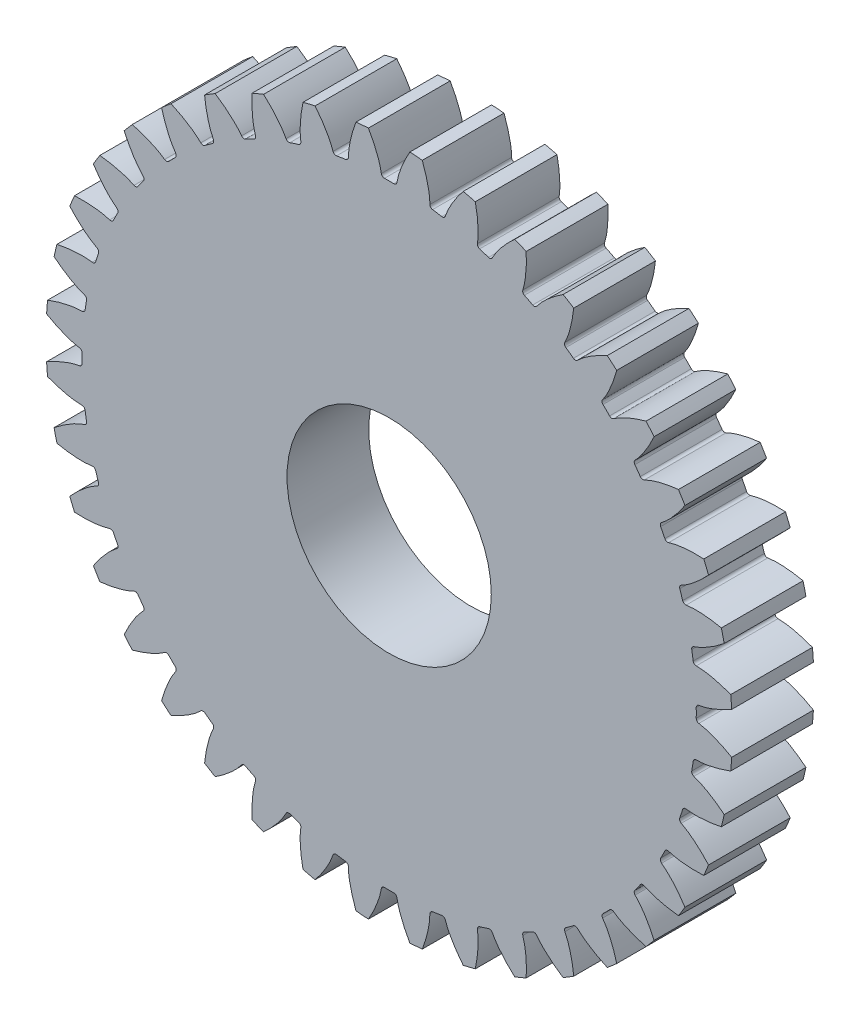
SolidWorks part; units mm, degrees
ref_plane "前视基准面" through (0, 0, 0) normal (0, 0, 1) x (1, 0, 0)
ref_plane "上视基准面" through (0, 0, 0) normal (0, 1, 0) x (1, 0, 0)
ref_plane "右视基准面" through (0, 0, 0) normal (1, 0, 0) x (0, 0, -1)
other "Configuration Table"
sketch "circles" plane through (0, 0, 0) normal (0, 0, 1) x (1, 0, 0)
  circle A0 centre (0, 0) radius 42
  circle A1 centre (0, 0) radius 37.5
  circle A2 centre (0, 0) radius 37.5877
  circle A3 centre (0, 0) radius 40
  dimension "D1" = 80
  dimension "D2" = 75.1754
  dimension "D3" = 75
  dimension "D4" = 84
extrude "Gear_extrude" add sketch "circles" along normal blind 10 contours A0
sketch "Involute" plane through (0, 0, 10) normal (0, 0, 1) x (1, 0, 0)
  spline S0 degree 4 poles (37.5765, -0.9158) (37.645, -0.9197) (37.8365, -0.9378) (38.1956, -0.9998) (38.7736, -1.1397) (39.4958, -1.3743) (40.4079, -1.7407) (41.4503, -2.2517) (42.5565, -2.8942) (44.0013, -3.8723) (45.3632, -4.9668) (46.643, -6.1553) (48.0474, -7.6399) (49.3628, -9.2047) (50.7742, -11.1387) (52.2189, -13.4708) (53.5152, -15.946) (54.6413, -18.5029) (55.482, -20.7981) (56.1023, -22.7989) (56.5537, -24.4844) (56.8762, -25.8433) (57.2316, -27.5509) (57.5244, -29.2733) (57.7561, -31.0004) (57.9277, -32.7411) (58.03, -34.1262) (58.0885, -35.3596) (58.118, -36.3844) (58.1271, -37.2927) (58.1284, -37.9211) (58.117, -38.7156) (58.1053, -39.2113) (58.0822, -39.9153) (58.058, -40.4457) (58.0262, -41.0523) (57.9901, -41.6142) (57.9477, -42.2028) (57.9003, -42.7733) (57.8604, -43.2108) (57.8321, -43.4973) (57.8175, -43.6418) knots 0 0 0 0 0 0.005377 0.015084 0.028532 0.04661 0.064855 0.092111 0.119476 0.146842 0.201575 0.228941 0.256307 0.307035 0.361767 0.4165 0.471232 0.525964 0.580697 0.608063 0.635429 0.662795 0.690161 0.744894 0.77226 0.799626 0.826992 0.854358 0.868042 0.881725 0.895408 0.909091 0.920455 0.931818 0.943182 0.954545 0.965909 0.977273 0.988636 1 1 1 1 1 construction
  spline S2 degree 4 poles (37.5765, 0.9158) (37.645, 0.9197) (37.8365, 0.9378) (38.1956, 0.9998) (38.7736, 1.1397) (39.4958, 1.3743) (40.4079, 1.7407) (41.4503, 2.2517) (42.5565, 2.8942) (44.0013, 3.8723) (45.3632, 4.9668) (46.643, 6.1553) (48.0474, 7.6399) (49.3628, 9.2047) (50.7742, 11.1387) (52.2189, 13.4708) (53.5152, 15.946) (54.6413, 18.5029) (55.482, 20.7981) (56.1023, 22.7989) (56.5537, 24.4844) (56.8762, 25.8433) (57.2316, 27.5509) (57.5244, 29.2733) (57.7561, 31.0004) (57.9277, 32.7411) (58.03, 34.1262) (58.0885, 35.3596) (58.118, 36.3844) (58.1271, 37.2927) (58.1284, 37.9211) (58.117, 38.7156) (58.1053, 39.2113) (58.0822, 39.9153) (58.058, 40.4457) (58.0262, 41.0523) (57.9901, 41.6142) (57.9477, 42.2028) (57.9003, 42.7733) (57.8604, 43.2108) (57.8321, 43.4973) (57.8175, 43.6418) knots 0 0 0 0 0 0.005377 0.015084 0.028532 0.04661 0.064855 0.092111 0.119476 0.146842 0.201575 0.228941 0.256307 0.307035 0.361767 0.4165 0.471232 0.525964 0.580697 0.608063 0.635429 0.662795 0.690161 0.744894 0.77226 0.799626 0.826992 0.854358 0.868042 0.881725 0.895408 0.909091 0.920455 0.931818 0.943182 0.954545 0.965909 0.977273 0.988636 1 1 1 1 1 construction
  spline S3 degree 4 poles (37.5765, 0.9158) (37.645, 0.9197) (37.8365, 0.9378) (38.1956, 0.9998) (38.7736, 1.1397) (39.4958, 1.3743) (40.4079, 1.7407) (41.4503, 2.2517) (42.5565, 2.8942) (44.0013, 3.8723) (45.3632, 4.9668) (46.643, 6.1553) (48.0474, 7.6399) (49.3628, 9.2047) (50.7742, 11.1387) (52.2189, 13.4708) (53.5152, 15.946) (54.6413, 18.5029) (55.482, 20.7981) (56.1023, 22.7989) (56.5537, 24.4844) (56.8762, 25.8433) (57.2316, 27.5509) (57.5244, 29.2733) (57.7561, 31.0004) (57.9277, 32.7411) (58.03, 34.1262) (58.0885, 35.3596) (58.118, 36.3844) (58.1271, 37.2927) (58.1284, 37.9211) (58.1195, 38.5434) (58.1132, 38.8564) (58.1093, 39.015) knots 0 0 0 0 0 0.005377 0.015084 0.028532 0.04661 0.064855 0.092111 0.119476 0.146842 0.201575 0.228941 0.256307 0.307035 0.361767 0.4165 0.471232 0.525964 0.580697 0.608063 0.635429 0.662795 0.690161 0.744894 0.77226 0.799626 0.826992 0.854358 0.868042 0.881725 0.895408 0.909091 0.909091 0.909091 0.909091 0.909091
  spline S4 degree 4 poles (37.5765, -0.9158) (37.645, -0.9197) (37.8365, -0.9378) (38.1956, -0.9998) (38.7736, -1.1397) (39.4958, -1.3743) (40.4079, -1.7407) (41.4503, -2.2517) (42.5565, -2.8942) (44.0013, -3.8723) (45.3632, -4.9668) (46.643, -6.1553) (48.0474, -7.6399) (49.3628, -9.2047) (50.7742, -11.1387) (52.2189, -13.4708) (53.5152, -15.946) (54.6413, -18.5029) (55.482, -20.7981) (56.1023, -22.7989) (56.5537, -24.4844) (56.8762, -25.8433) (57.2316, -27.5509) (57.5244, -29.2733) (57.7561, -31.0004) (57.9277, -32.7411) (58.03, -34.1262) (58.0885, -35.3596) (58.118, -36.3844) (58.1271, -37.2927) (58.1284, -37.9211) (58.1195, -38.5434) (58.1132, -38.8564) (58.1093, -39.015) knots 0 0 0 0 0 0.005377 0.015084 0.028532 0.04661 0.064855 0.092111 0.119476 0.146842 0.201575 0.228941 0.256307 0.307035 0.361767 0.4165 0.471232 0.525964 0.580697 0.608063 0.635429 0.662795 0.690161 0.744894 0.77226 0.799626 0.826992 0.854358 0.868042 0.881725 0.895408 0.909091 0.909091 0.909091 0.909091 0.909091
sketch "Db>Df" plane through (0, 0, 10) normal (0, 0, 1) x (1, 0, 0)
  line L2 (0, 0) -> (39.9692, 1.5704) construction
  line L3 (0, 0) -> (80.296, -3.1548) construction
  line L4 (58.1093, 39.015) -> (80.296, -3.1548)
  line L5 (80.296, -3.1548) -> (58.1093, -39.015)
  circle A2 centre (0, 0) radius 40 construction
  circle A3 centre (0, 0) radius 37.5877 construction
  arc A4 (37.5765, -0.9158) -> (37.5765, 0.9158) centre (0, 0) ccw
  spline S0 degree 4 poles (-26.0717, -1999.6596) (24.9859, -56.3104) (30.7419, -1.8226) (34.9218, -0.2072) (38.7736, -1.1397) (39.4958, -1.3743) (40.4079, -1.7407) (41.4503, -2.2517) (42.5565, -2.8942) (44.0013, -3.8723) (45.3632, -4.9668) (46.643, -6.1553) (48.0474, -7.6399) (49.3628, -9.2047) (50.7742, -11.1387) (52.2189, -13.4708) (53.5152, -15.946) (54.6413, -18.5029) (55.482, -20.7981) (56.1023, -22.7989) (56.5537, -24.4844) (56.8762, -25.8433) (57.2316, -27.5509) (57.5244, -29.2733) (57.7561, -31.0004) (57.9277, -32.7411) (58.03, -34.1262) (58.0885, -35.3596) (58.118, -36.3844) (58.1271, -37.2927) (58.1329, -40.071) (57.8308, -47.3652) (59.2715, 23.1595) (8.6455, -2038.0427) knots -0.263995 -0.263995 -0.263995 -0.263995 -0.263995 0.005377 0.015084 0.028532 0.04661 0.064855 0.092111 0.119476 0.146842 0.201575 0.228941 0.256307 0.307035 0.361767 0.4165 0.471232 0.525964 0.580697 0.608063 0.635429 0.662795 0.690161 0.744894 0.77226 0.799626 0.826992 0.854358 0.868042 0.881725 0.895408 1.096362 1.096362 1.096362 1.096362 1.096362 only from (37.5765, -0.9158) to (58.1093, -39.015) construction
  spline S1 degree 4 poles (-26.0717, 1999.6596) (24.9859, 56.3104) (30.7419, 1.8226) (34.9218, 0.2072) (38.7736, 1.1397) (39.4958, 1.3743) (40.4079, 1.7407) (41.4503, 2.2517) (42.5565, 2.8942) (44.0013, 3.8723) (45.3632, 4.9668) (46.643, 6.1553) (48.0474, 7.6399) (49.3628, 9.2047) (50.7742, 11.1387) (52.2189, 13.4708) (53.5152, 15.946) (54.6413, 18.5029) (55.482, 20.7981) (56.1023, 22.7989) (56.5537, 24.4844) (56.8762, 25.8433) (57.2316, 27.5509) (57.5244, 29.2733) (57.7561, 31.0004) (57.9277, 32.7411) (58.03, 34.1262) (58.0885, 35.3596) (58.118, 36.3844) (58.1271, 37.2927) (58.1329, 40.071) (57.8308, 47.3652) (59.2715, -23.1595) (8.6455, 2038.0427) knots -0.263995 -0.263995 -0.263995 -0.263995 -0.263995 0.005377 0.015084 0.028532 0.04661 0.064855 0.092111 0.119476 0.146842 0.201575 0.228941 0.256307 0.307035 0.361767 0.4165 0.471232 0.525964 0.580697 0.608063 0.635429 0.662795 0.690161 0.744894 0.77226 0.799626 0.826992 0.854358 0.868042 0.881725 0.895408 1.096362 1.096362 1.096362 1.096362 1.096362 only from (37.5765, 0.9158) to (58.1093, 39.015) construction
  spline S2 degree 4 poles (37.5765, -0.9158) (37.645, -0.9197) (37.8365, -0.9378) (38.1956, -0.9998) (38.7736, -1.1397) (39.4958, -1.3743) (40.4079, -1.7407) (41.4503, -2.2517) (42.5565, -2.8942) (44.0013, -3.8723) (45.3632, -4.9668) (46.643, -6.1553) (48.0474, -7.6399) (49.3628, -9.2047) (50.7742, -11.1387) (52.2189, -13.4708) (53.5152, -15.946) (54.6413, -18.5029) (55.482, -20.7981) (56.1023, -22.7989) (56.5537, -24.4844) (56.8762, -25.8433) (57.2316, -27.5509) (57.5244, -29.2733) (57.7561, -31.0004) (57.9277, -32.7411) (58.03, -34.1262) (58.0885, -35.3596) (58.118, -36.3844) (58.1271, -37.2927) (58.1284, -37.9211) (58.1195, -38.5434) (58.1132, -38.8564) (58.1093, -39.015) knots 0 0 0 0 0 0.005377 0.015084 0.028532 0.04661 0.064855 0.092111 0.119476 0.146842 0.201575 0.228941 0.256307 0.307035 0.361767 0.4165 0.471232 0.525964 0.580697 0.608063 0.635429 0.662795 0.690161 0.744894 0.77226 0.799626 0.826992 0.854358 0.868042 0.881725 0.895408 0.909091 0.909091 0.909091 0.909091 0.909091
  spline S3 degree 4 poles (37.5765, 0.9158) (37.645, 0.9197) (37.8365, 0.9378) (38.1956, 0.9998) (38.7736, 1.1397) (39.4958, 1.3743) (40.4079, 1.7407) (41.4503, 2.2517) (42.5565, 2.8942) (44.0013, 3.8723) (45.3632, 4.9668) (46.643, 6.1553) (48.0474, 7.6399) (49.3628, 9.2047) (50.7742, 11.1387) (52.2189, 13.4708) (53.5152, 15.946) (54.6413, 18.5029) (55.482, 20.7981) (56.1023, 22.7989) (56.5537, 24.4844) (56.8762, 25.8433) (57.2316, 27.5509) (57.5244, 29.2733) (57.7561, 31.0004) (57.9277, 32.7411) (58.03, 34.1262) (58.0885, 35.3596) (58.118, 36.3844) (58.1271, 37.2927) (58.1284, 37.9211) (58.1195, 38.5434) (58.1132, 38.8564) (58.1093, 39.015) knots 0 0 0 0 0 0.005377 0.015084 0.028532 0.04661 0.064855 0.092111 0.119476 0.146842 0.201575 0.228941 0.256307 0.307035 0.361767 0.4165 0.471232 0.525964 0.580697 0.608063 0.635429 0.662795 0.690161 0.744894 0.77226 0.799626 0.826992 0.854358 0.868042 0.881725 0.895408 0.909091 0.909091 0.909091 0.909091 0.909091
  dimension "D1" = 4.5
  dimension "D2" = 60
extrude "extruded-cut1" cut sketch "Db>Df" against normal through all
fillet "fillet1" radius 0.38 2 edges at (37.5765, -0.9158, 5) (37.5765, 0.9158, 5)
pattern_circular "circular-parttern1" count 40 over 360 about axis through (0, 0, 10) along (0, 0, -1) of "extruded-cut1", "fillet1" reverse direction yes
sketch "Db<Df" [suppressed] plane through (0, 0, 10) normal (0, 0, 1) x (1, 0, 0)
  line L0 (0, 0) -> (100.8439, 0) construction
  line L1 (0, 0) -> (49.9753, 1.5705) construction
  line L2 (73.0175, 48.1968) -> (100.8439, 0)
  line L3 (100.8439, 0) -> (73.0175, -48.1968)
  circle A0 centre (0, 0) radius 47.5 construction
  arc A1 (47.4927, -0.8355) -> (47.4927, 0.8355) centre (0, 0) ccw
  circle A2 centre (0, 0) radius 50 construction
  spline S0 degree 4 poles (69.1798, -1998.5936) (37.8966, 59.197) (41.8514, 1.7937) (44.8419, 0.3903) (47.7946, 0.8837) (48.4767, 1.0444) (49.3818, 1.3297) (50.5254, 1.7793) (51.8333, 2.4075) (53.2224, 3.1999) (54.6746, 4.1663) (56.0658, 5.2211) (57.3956, 6.3522) (58.6648, 7.5507) (60.1325, 9.0778) (61.7919, 11.0209) (63.5752, 13.4244) (65.4038, 16.3254) (67.0485, 19.4065) (68.4812, 22.5914) (69.5546, 25.4522) (70.3495, 27.9469) (70.9303, 30.0495) (71.3467, 31.7445) (71.7156, 33.4497) (72.0375, 35.1657) (72.3133, 36.8876) (72.5435, 38.6195) (72.7289, 40.3511) (72.8524, 41.8792) (72.9313, 43.1759) (72.9787, 44.2811) (73.0067, 45.1233) (73.0226, 46.0516) (73.0565, 49.344) (72.7733, 58.0548) (73.7264, -18.7455) (39.1601, 2047.4863) knots -0.159153 -0.159153 -0.159153 -0.159153 -0.159153 0.002688 0.005377 0.015084 0.028532 0.04661 0.064855 0.092111 0.119476 0.146842 0.174209 0.201575 0.228941 0.256307 0.307035 0.361767 0.4165 0.471232 0.525964 0.580697 0.608063 0.635429 0.662795 0.690161 0.717528 0.744894 0.77226 0.799626 0.826992 0.840675 0.854358 0.868042 0.881725 0.895408 1.086914 1.086914 1.086914 1.086914 1.086914 only from (46.9782, 0.7758) to (73.0175, 48.1968) construction
  spline S1 degree 4 poles (47.4927, 0.8355) (47.602, 0.8537) (47.9217, 0.9139) (48.5186, 1.0576) (49.3818, 1.3297) (50.5254, 1.7793) (51.8333, 2.4075) (53.2224, 3.1999) (54.6746, 4.1663) (56.0658, 5.2211) (57.3956, 6.3522) (58.6648, 7.5507) (60.1325, 9.0778) (61.7919, 11.0209) (63.5752, 13.4244) (65.4038, 16.3254) (67.0485, 19.4065) (68.4812, 22.5914) (69.5546, 25.4522) (70.3495, 27.9469) (70.9303, 30.0495) (71.3467, 31.7445) (71.7156, 33.4497) (72.0375, 35.1657) (72.3133, 36.8876) (72.5435, 38.6195) (72.7289, 40.3511) (72.8524, 41.8792) (72.9313, 43.1759) (72.9787, 44.2811) (73.0067, 45.1233) (73.0226, 46.0516) (73.0306, 46.8265) (73.0255, 47.605) (73.0207, 47.9985) (73.0175, 48.1968) knots 0.008127 0.008127 0.008127 0.008127 0.008127 0.015084 0.028532 0.04661 0.064855 0.092111 0.119476 0.146842 0.174209 0.201575 0.228941 0.256307 0.307035 0.361767 0.4165 0.471232 0.525964 0.580697 0.608063 0.635429 0.662795 0.690161 0.717528 0.744894 0.77226 0.799626 0.826992 0.840675 0.854358 0.868042 0.881725 0.895408 0.909091 0.909091 0.909091 0.909091 0.909091
  spline S2 degree 4 poles (69.1798, 1998.5936) (37.8966, -59.197) (41.8514, -1.7937) (44.8419, -0.3903) (47.7946, -0.8837) (48.4767, -1.0444) (49.3818, -1.3297) (50.5254, -1.7793) (51.8333, -2.4075) (53.2224, -3.1999) (54.6746, -4.1663) (56.0658, -5.2211) (57.3956, -6.3522) (58.6648, -7.5507) (60.1325, -9.0778) (61.7919, -11.0209) (63.5752, -13.4244) (65.4038, -16.3254) (67.0485, -19.4065) (68.4812, -22.5914) (69.5546, -25.4522) (70.3495, -27.9469) (70.9303, -30.0495) (71.3467, -31.7445) (71.7156, -33.4497) (72.0375, -35.1657) (72.3133, -36.8876) (72.5435, -38.6195) (72.7289, -40.3511) (72.8524, -41.8792) (72.9313, -43.1759) (72.9787, -44.2811) (73.0067, -45.1233) (73.0226, -46.0516) (73.0565, -49.344) (72.7733, -58.0548) (73.7264, 18.7455) (39.1601, -2047.4863) knots -0.159153 -0.159153 -0.159153 -0.159153 -0.159153 0.002688 0.005377 0.015084 0.028532 0.04661 0.064855 0.092111 0.119476 0.146842 0.174209 0.201575 0.228941 0.256307 0.307035 0.361767 0.4165 0.471232 0.525964 0.580697 0.608063 0.635429 0.662795 0.690161 0.717528 0.744894 0.77226 0.799626 0.826992 0.840675 0.854358 0.868042 0.881725 0.895408 1.086914 1.086914 1.086914 1.086914 1.086914 only from (46.9782, -0.7758) to (73.0175, -48.1968) construction
  spline S3 degree 4 poles (47.4927, -0.8355) (47.602, -0.8537) (47.9217, -0.9139) (48.5186, -1.0576) (49.3818, -1.3297) (50.5254, -1.7793) (51.8333, -2.4075) (53.2224, -3.1999) (54.6746, -4.1663) (56.0658, -5.2211) (57.3956, -6.3522) (58.6648, -7.5507) (60.1325, -9.0778) (61.7919, -11.0209) (63.5752, -13.4244) (65.4038, -16.3254) (67.0485, -19.4065) (68.4812, -22.5914) (69.5546, -25.4522) (70.3495, -27.9469) (70.9303, -30.0495) (71.3467, -31.7445) (71.7156, -33.4497) (72.0375, -35.1657) (72.3133, -36.8876) (72.5435, -38.6195) (72.7289, -40.3511) (72.8524, -41.8792) (72.9313, -43.1759) (72.9787, -44.2811) (73.0067, -45.1233) (73.0226, -46.0516) (73.0306, -46.8265) (73.0255, -47.605) (73.0207, -47.9985) (73.0175, -48.1968) knots 0.008127 0.008127 0.008127 0.008127 0.008127 0.015084 0.028532 0.04661 0.064855 0.092111 0.119476 0.146842 0.174209 0.201575 0.228941 0.256307 0.307035 0.361767 0.4165 0.471232 0.525964 0.580697 0.608063 0.635429 0.662795 0.690161 0.717528 0.744894 0.77226 0.799626 0.826992 0.840675 0.854358 0.868042 0.881725 0.895408 0.909091 0.909091 0.909091 0.909091 0.909091
  dimension "D1" = 2.25
  dimension "D2" = 60
extrude "extruded-cut2" [suppressed] cut sketch "Db<Df" against normal through all
fillet "fillet2" [suppressed] radius 0.38
pattern_circular "circular-parttern2" [suppressed] count 40 over 360 of bodies 109
sketch "Sketch1" plane through (0, 0, 0) normal (0, 0, 1) x (1, 0, 0)
  circle A0 centre (0, 0) radius 12.5
extrude "Cut-Extrude1" cut sketch "Sketch1" along normal blind 10
sketch3d "3DSketch1"
  line L0 (0, 0, 0) -> (0, 0, 1000) construction
ref_axis "shaft_axis" through (0, 0, 0) along (0, 0, 1)
ref_plane "front_face" through (0, 0, 5) normal (0, 0, 1) x (1, 0, 0)
ref_plane "back_face" through (0, 0, -5) normal (0, 0, 1) x (1, 0, 0)
ref_plane "gear_mid_plane" through (0, 0, 0) normal (0, 0, 1) x (1, 0, 0)
equation "\"M\" = 2mm"
equation "\"Z\" = 40"
equation "\"B\" = 10mm"
equation "\"Alpha\"= 20\t'压力角"
equation "\"D\"= \"M\"*\"Z\"   '分度圆"
equation "\"Db\"= \"D\" * cos ( \"Alpha\" )  \t'基圆"
equation "\"Hax\" = 1"
equation "\"Cx\" = 0.25"
equation "\"Ha\"= \"Hax\" * \"M\"\t'齿顶高"
equation "\"Hf\"= ( \"Hax\" + \"Cx\" ) * \"M\"\t'齿根高"
equation "\"Df\"= \"D\" - 2 * \"Hf\"\t\t'齿根圆"
equation "\"Da\"= \"D\" + 2 * \"Ha\"\t'齿顶圆"
equation "\"Theta\"= 360 * sqr ( ( 1 / cos ( \"Alpha\" ) ) ^ 2 - 1 ) / ( 2 * pi ) - atn ( sqr ( ( 1 / cos ( \"Alpha\" ) ) ^ 2 - 1 ) )"
equation "\"Phi\"= - ( 2 * pi * ( 90 / \"Z\" - \"Theta\" ) / 360 )"
equation "\"D1@circles\" = \"D\""
equation "\"D2@circles\" = \"Db\""
equation "\"D3@circles\" = \"Df\""
equation "\"D4@circles\" = \"Da\""
equation "\"D1@Gear_extrude\" = \"B\""
equation "\"D1@circular-parttern1\" = \"Z\""
equation "\"Db>Df\"= IIF ( \"Db\" > \"Df\" ,  unsuppressed  ,  suppressed  ) "
equation "\"extruded-cut1\"= IIF ( \"Db\" > \"Df\" ,  unsuppressed  ,  suppressed  ) "
equation "\"D1@Db<Df\"=90/\"Z\""
equation "\"D1@fillet1\" = 0.19 * \"M\""
equation "\"Db<Df\" = IIF ( \"Db\" < \"Df\" , \"unsuppressed\" , \"suppressed\" )"
equation "\"extruded-cut2\"= IIF ( \"Db\" < \"Df\" ,  unsuppressed  ,  suppressed  ) "
equation "\"D1@fillet2\" = 0.19 * \"M\""
equation "\"D1@circular-parttern2\" = \"Z\""
equation "\"circular-parttern2\"= IIF ( \"Db\" < \"Df\" ,  unsuppressed  ,  suppressed  ) "
equation "\"fillet1\"= IIF ( \"Db\" > \"Df\" ,  unsuppressed  ,  suppressed  ) "
equation "\"fillet2\"= IIF ( \"Db\" < \"Df\" ,  unsuppressed  ,  suppressed  ) "
equation "\"circular-parttern1\"= IIF ( \"Db\" > \"Df\" , \"unsuppressed\" , \"suppressed\" )"
